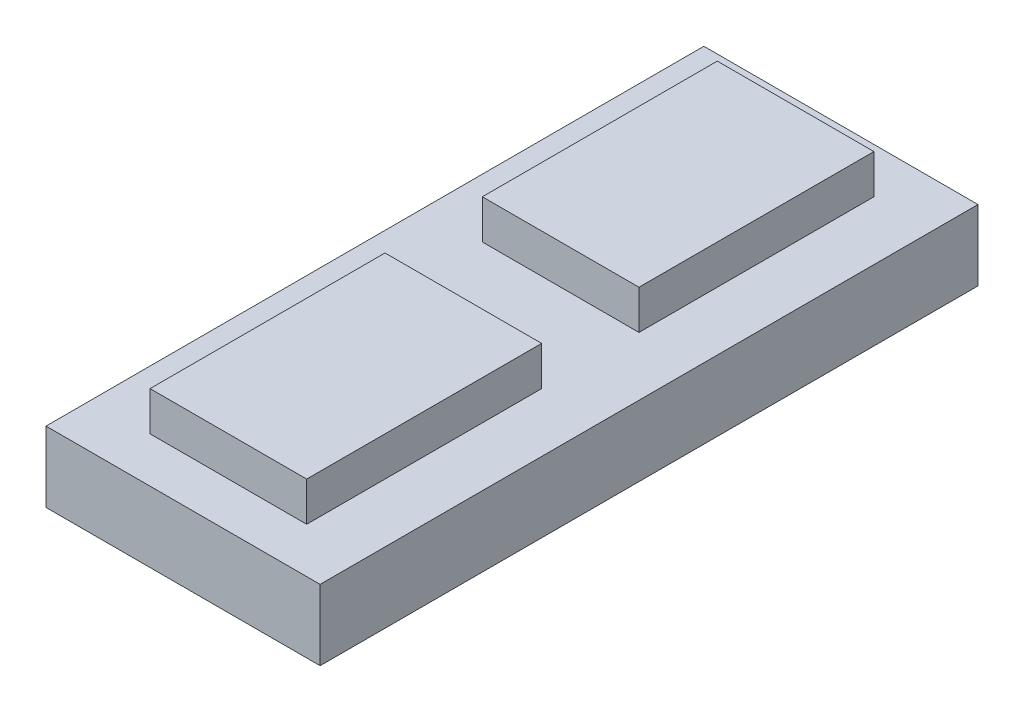
SolidWorks part; units mm, degrees
ref_plane "Front Plane" through (0, 0, 0) normal (0, 0, 1) x (1, 0, 0)
ref_plane "Top Plane" through (0, 0, 0) normal (0, 1, 0) x (1, 0, 0)
ref_plane "Right Plane" through (0, 0, 0) normal (1, 0, 0) x (0, 0, -1)
sketch "Sketch1" plane through (0, 0, 0) normal (0, 1, 0) x (1, 0, 0)
  line L1 (-17.5, 42) -> (17.5, 42)
  line L2 (-17.5, 42) -> (-17.5, -42)
  line L3 (-17.5, -42) -> (17.5, -42)
  line L4 (17.5, 42) -> (17.5, -42)
  line L5 (-17.5, 42) -> (17.5, -42) construction
  line L6 (-17.5, -42) -> (17.5, 42) construction
  point P0 (0, 0)
  dimension "D1" = 84
  dimension "D2" = 35
extrude "Boss-Extrude1" add sketch "Sketch1" along normal blind 9
sketch "Sketch2" plane through (0, 9, 0) normal (0, 1, 0) x (1, 0, 0)
  line L1 (-10, 36.2132) -> (10, 36.2132)
  line L2 (-10, 36.2132) -> (-10, -36.2132)
  line L3 (-10, -36.2132) -> (10, -36.2132)
  line L4 (10, 36.2132) -> (10, -36.2132)
  line L5 (-10, 36.2132) -> (10, -36.2132) construction
  line L6 (-10, -36.2132) -> (10, 36.2132) construction
  line L7 (-10, 6.2132) -> (10, 6.2132)
  line L8 (-10, 6.2132) -> (-10, -6.2132)
  line L9 (-10, -6.2132) -> (10, -6.2132)
  line L10 (10, 6.2132) -> (10, -6.2132)
  line L11 (-10, 6.2132) -> (10, -6.2132) construction
  line L12 (-10, -6.2132) -> (10, 6.2132) construction
  point P0 (0, 0)
  point P6 (0, 0)
  dimension "D1" = 30
  dimension "D2" = 20
extrude "Boss-Extrude2" add sketch "Sketch2" along normal blind 5 separate body contours L2 L7 L4 L1 | L9 L2 L3 L4 region at (0, 9, -21.2132) region at (0, 9, 21.2132)
